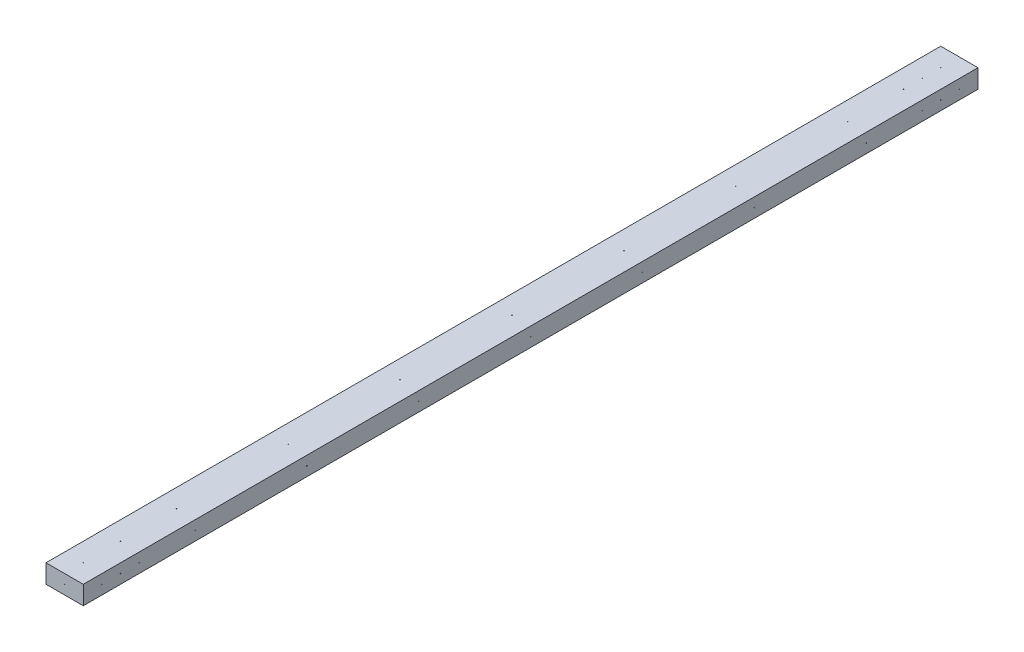
SolidWorks part; units mm, degrees
material "Pine"
ref_plane "Front Plane" through (0, 0, 0) normal (0, 0, 1) x (1, 0, 0)
ref_plane "Top Plane" through (0, 0, 0) normal (0, 1, 0) x (1, 0, 0)
ref_plane "Right Plane" through (0, 0, 0) normal (1, 0, 0) x (0, 0, -1)
sketch "Sketch1" plane through (0, 0, 0) normal (0, 0, 1) x (1, 0, 0)
  line L1 (0, 0) -> (101.6, 0)
  line L2 (0, 0) -> (0, 50.8)
  line L3 (0, 50.8) -> (101.6, 50.8)
  line L4 (101.6, 0) -> (101.6, 50.8)
  dimension "D1" = 101.6
  dimension "D2" = 50.8
extrude "Boss-Extrude1" add sketch "Sketch1" along normal blind 2438.4
sketch "Sketch2" plane through (0, 50.8, 0) normal (0, 1, 0) x (1, 0, 0)
  line L0 (50.8, 0) -> (50.8, -304.8) construction
  line L1 (101.6, 0) -> (0, 0) construction
  line L2 (0, 0) -> (0, -2438.4)
  circle A0 centre (50.8, -304.8) radius 0.8763
  dimension "D2" = 1.7526
  dimension "D1" = 304.8
extrude "Cut-Extrude1" cut sketch "Sketch2" against normal up to surface (50.8 mm away) contours A0 region at (50.8, 50.8, 304.8) up to face at (50.8, 0, 1219.2)
pattern_linear "LPattern1" count 7 spacing 304.8 along (0, 0, 1) of "Cut-Extrude1"
sketch "Sketch3" plane through (0, 50.8, 0) normal (0, 1, 0) x (1, 0, 0)
  line L0 (50.8, 0) -> (50.8, -50.8) construction
  line L1 (101.6, 0) -> (0, 0) construction
  line L2 (101.6, -1219.2) -> (0, -1219.2) construction
  line L3 (101.6, -2438.4) -> (101.6, 0) construction
  line L4 (0, -2438.4) -> (0, 0) construction
  circle A0 centre (50.8, -50.8) radius 0.8763
  circle A1 centre (50.8, -2286) radius 0.8763
  circle A2 centre (50.8, -101.6) radius 0.8763
  circle A3 centre (50.8, -152.4) radius 0.8763
  circle A4 centre (50.8, -2336.8) radius 0.8763
  circle A5 centre (50.8, -2387.6) radius 0.8763
  dimension "D2" = 1.7526
  dimension "D1" = 50.8
  dimension "D3" = 3
extrude "Cut-Extrude2" cut sketch "Sketch3" against normal up to surface (50.8 mm away) up to face at (50.8, 0, 2134.4763)
sketch "Sketch4" plane through (0, 0, 2438.4) normal (0, 0, 1) x (1, 0, 0)
  line L0 (0, 50.8) -> (101.6, 0) construction
  line L1 (101.6, 50.8) -> (0, 0) construction
  circle A0 centre (50.8, 25.4) radius 0.8763
  dimension "D1" = 1.7526
extrude "Cut-Extrude3" cut sketch "Sketch4" against normal up to surface (2438.4 mm away) up to face at (50.8, 25.4, 0)
sketch "Sketch6" plane through (0, 0, 0) normal (-1, 0, 0) x (0, 0, 1)
  line L0 (0, 25.4) -> (304.8, 25.4) construction
  line L1 (0, 50.8) -> (0, 0) construction
  circle A0 centre (304.8, 25.4) radius 0.8763
  circle A1 centre (609.6, 25.4) radius 0.8763
  circle A2 centre (914.4, 25.4) radius 0.8763
  circle A3 centre (1219.2, 25.4) radius 0.8763
  circle A4 centre (1524, 25.4) radius 0.8763
  circle A5 centre (1828.8, 25.4) radius 0.8763
  circle A6 centre (2133.6, 25.4) radius 0.8763
  dimension "D2" = 1.7526
  dimension "D1" = 304.8
  dimension "D3" = 7
extrude "Cut-Extrude4" cut sketch "Sketch6" against normal up to surface (101.6 mm away) up to face at (101.6, 25.4, 1219.2)
sketch "Sketch7" plane through (0, 0, 0) normal (-1, 0, 0) x (0, 0, 1)
  line L0 (0, 25.4) -> (50.8, 25.4) construction
  line L1 (0, 50.8) -> (0, 0) construction
  line L2 (1219.2, 0) -> (1219.2, 50.8) construction
  line L3 (2438.4, 0) -> (0, 0) construction
  line L4 (2438.4, 50.8) -> (0, 50.8) construction
  circle A0 centre (50.8, 25.4) radius 0.8763
  circle A1 centre (101.6, 25.4) radius 0.8763
  circle A2 centre (152.4, 25.4) radius 0.8763
  circle A3 centre (2286, 25.4) radius 0.8763
  circle A4 centre (2336.8, 25.4) radius 0.8763
  circle A5 centre (2387.6, 25.4) radius 0.8763
  dimension "D1" = 1.7526
  dimension "D2" = 50.8
  dimension "D3" = 3
extrude "Cut-Extrude5" cut sketch "Sketch7" against normal up to surface (101.6 mm away) up to face at (101.6, 25.4, 2134.4763)
equation "\"length\"= 1219.2 * 2"
equation "\"D1@Boss-Extrude1\"=\"length\""
equation "\"D1@LPattern1\" = \"length\" / 304.8 - 1"
equation "\"D3@Sketch6\"=\"length\" / 304.8 - 1"
